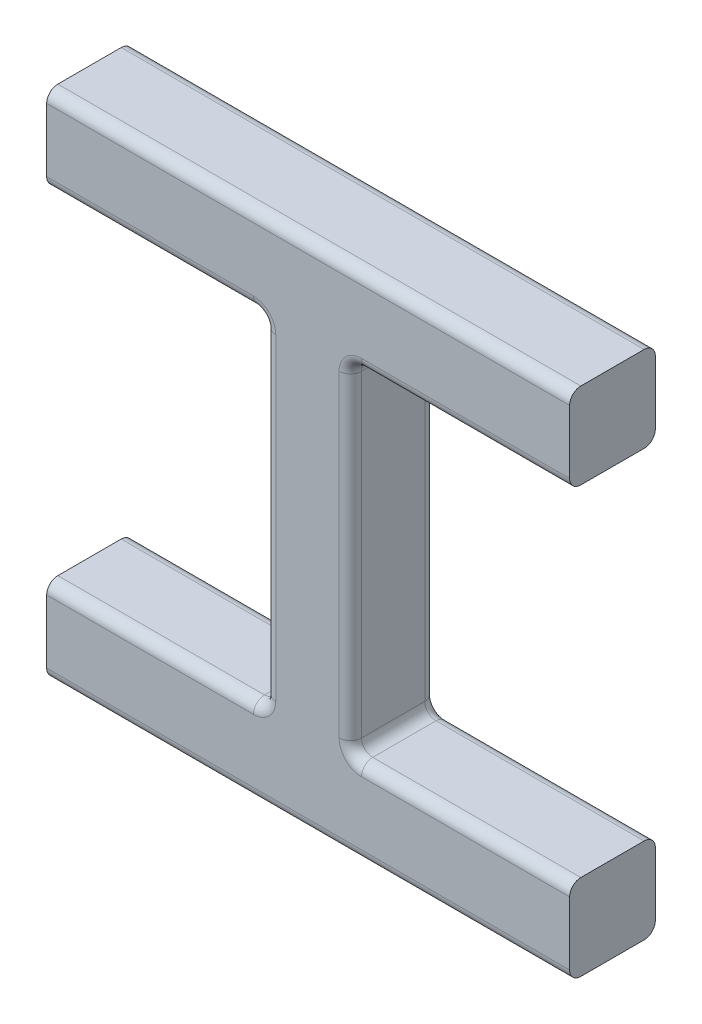
SolidWorks part; units mm, degrees
material "Cast Alloy Steel"
ref_plane "Front Plane" through (0, 0, 0) normal (0, 0, 1) x (1, 0, 0)
ref_plane "Top Plane" through (0, 0, 0) normal (0, 1, 0) x (1, 0, 0)
ref_plane "Right Plane" through (0, 0, 0) normal (1, 0, 0) x (0, 0, -1)
sketch "Sketch1" plane through (0, 0, 0) normal (0, 0, 1) x (1, 0, 0)
  line L0 (0, 759.8125) -> (0, 912.8125)
  line L1 (0, 0) -> (933.45, 0)
  line L2 (0, 0) -> (0, 153)
  line L3 (0, 912.8125) -> (933.45, 912.8125)
  line L4 (933.45, 0) -> (933.45, 153)
  line L5 (0, 759.8125) -> (388.9375, 759.8125)
  line L6 (933.45, 759.8125) -> (933.45, 912.8125)
  line L7 (0, 153) -> (388.9375, 153)
  line L8 (388.9375, 759.8125) -> (388.9375, 153)
  line L9 (933.45, 759.8125) -> (541.9375, 759.8125)
  line L11 (933.45, 153) -> (541.9375, 153)
  line L12 (541.9375, 759.8125) -> (541.9375, 153)
  dimension "D1" = 933.45
  dimension "D2" = 912.8125
  dimension "D3" = 153
  dimension "D4" = 153
  dimension "D5" = 388.9375
extrude "Boss-Extrude1" add sketch "Sketch1" along normal blind 153
fillet "Fillet2" radius 20 20 edges at (541.9375, 153, 76.5) (541.9375, 456.4062, 0) (388.9375, 456.4062, 0) (388.9375, 456.4062, 153) (541.9375, 456.4062, 153) (737.6938, 153, 0) (737.6938, 153, 153) (737.6937, 759.8125, 0) (737.6937, 759.8125, 153) (541.9375, 759.8125, 76.5) (466.725, 912.8125, 0) (466.725, 912.8125, 153) (466.725, 0, 0) (466.725, 0, 153) (194.4688, 153, 0) (194.4688, 153, 153) (388.9375, 153, 76.5) (388.9375, 759.8125, 76.5) (194.4688, 759.8125, 0) (194.4688, 759.8125, 153)
shell "Shell3" thickness 10 removed face at (466.0813, 456.4062, 0)
ref_plane "Plane1" through (0, 456.4062, 0) normal (0, -1, 0) x (-1, 0, 0)
